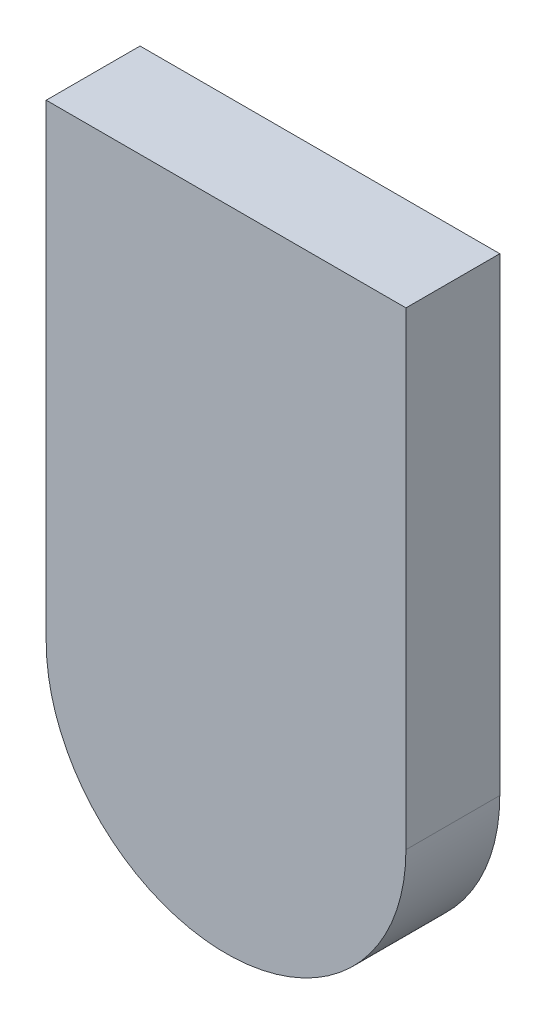
SolidWorks part; units mm, degrees
material "ABS"
ref_plane "Front Plane" through (0, 0, 0) normal (0, 0, 1) x (1, 0, 0)
ref_plane "Top Plane" through (0, 0, 0) normal (0, 1, 0) x (1, 0, 0)
ref_plane "Right Plane" through (0, 0, 0) normal (1, 0, 0) x (0, 0, -1)
ref_axis "X Axis" through (88.99, 0, 0) along (-1, 0, 0)
ref_axis "Y Axis" through (0, 55, 0) along (0, -1, 0)
ref_axis "Z Axis" through (0, 0, -88.99) along (0, 0, 1)
sketch "Sketch1" plane through (0, 0, 0) normal (0, 0, 1) x (1, 0, 0)
  line L1 (-11.5, 30) -> (11.5, 30)
  line L2 (-11.5, 30) -> (-11.5, 0)
  line L3 (-11.5, 0) -> (11.5, 0) construction
  line L4 (11.5, 30) -> (11.5, 0)
  line L5 (0, 0) -> (0, 30) construction
  line L6 (-11.5, 15) -> (11.5, 15) construction
  arc A0 (11.5, 0) -> (-11.5, 0) centre (0, 0) cw
  point P0 (0, 15)
  dimension "D1" = 23
  dimension "D2" = 30
extrude "Boss-Extrude1" add sketch "Sketch1" along normal blind 6
